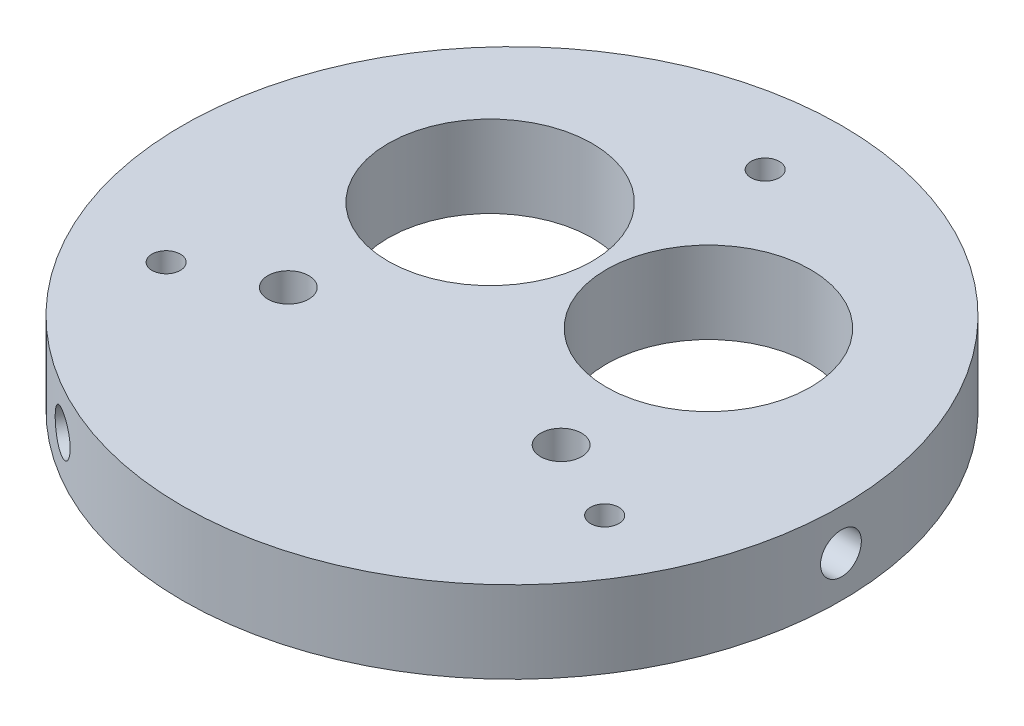
SolidWorks part; units mm, degrees
material "G10 Fiberglass"
ref_plane "Front Plane" through (0, 0, 0) normal (0, 0, 1) x (1, 0, 0)
ref_plane "Top Plane" through (0, 0, 0) normal (0, 1, 0) x (1, 0, 0)
ref_plane "Right Plane" through (0, 0, 0) normal (1, 0, 0) x (0, 0, -1)
sketch "Sketch1" plane through (0, 0, 0) normal (0, 1, 0) x (1, 0, 0)
  circle A0 centre (0, 0) radius 38.354
  dimension "D1" = 76.708
extrude "Boss-Extrude1" add sketch "Sketch1" along normal blind 9.525
sketch "Sketch2" plane through (0, 9.525, 0) normal (0, 1, 0) x (1, 0, 0)
  line L0 (12.7, 10.16) -> (-12.7, 10.16) construction
  line L3 (0, 6.35) -> (0, -19.05) construction
  line L4 (-14.6936, 35.4278) -> (-10.8624, 36.7836) construction
  line L5 (-14.6936, 35.4278) -> (-12.0454, 27.9451) construction
  line L6 (-10.8624, 36.7836) -> (-8.2143, 29.3009) construction
  line L7 (-12.0454, 27.9451) -> (-8.2143, 29.3009) construction
  line L8 (37.9022, -4.9723) -> (30.0979, -3.5244) construction
  line L9 (37.9022, -4.9723) -> (37.1609, -8.9682) construction
  line L10 (37.1609, -8.9682) -> (29.3566, -7.5202) construction
  line L11 (30.0979, -3.5244) -> (29.3566, -7.5202) construction
  line L12 (-23.3832, -30.3216) -> (-18.2271, -24.2869) construction
  line L13 (-23.3832, -30.3216) -> (-26.473, -27.6817) construction
  line L14 (-26.473, -27.6817) -> (-21.3169, -21.6469) construction
  line L15 (-18.2271, -24.2869) -> (-21.3169, -21.6469) construction
  line L16 (0, 10.16) -> (0, -18.415) construction
  line L17 (-12.7, 10.16) -> (12.7, 10.16) construction
  line L18 (-12.7, 24.13) -> (12.7, 24.13) construction
  line L19 (-12.7, -3.81) -> (12.7, -3.81) construction
  circle A0 centre (0, 0) radius 29.464 construction
  circle A1 centre (0, 29.464) radius 1.651
  circle A2 centre (25.5166, -14.732) radius 1.651
  circle A3 centre (-25.5166, -14.732) radius 1.651
  circle A4 centre (0, -18.415) radius 4.1275
  circle A7 centre (0, 0) radius 38.354 construction
  circle A8 centre (-12.7, 10.16) radius 11.8745
  circle A9 centre (12.7, 10.16) radius 11.8745
  circle A10 centre (0, 20.32) radius 3.175
  circle A11 centre (0, 0) radius 3.175
  arc A12 (-12.7, 24.13) -> (-12.7, -3.81) centre (-12.7, 10.16) ccw construction
  arc A13 (12.7, -3.81) -> (12.7, 24.13) centre (12.7, 10.16) ccw construction
  point P11 (0, 0)
  point P36 (-0.0582, 0.0446)
  point P38 (0, 10.16)
  dimension "D1" = 3.302
  dimension "D2" = 58.928
  dimension "D11" = 8.255
  dimension "D4" = 23.749
  dimension "D5" = 23.749
  dimension "D13" = 6.35
  dimension "D14" = 6.35
  dimension "D7" = 4.064
  dimension "D8" = 7.9375
  dimension "D6" = 10.16
  dimension "D10" = 25.4
  dimension "D12" = 28.575
  dimension "D15" = 27.94
  dimension "D17" = 3.81
  dimension "D16" = 3.81
  dimension "D3" = 3
  dimension "D9" = 3
extrude "Cut-Extrude1" cut sketch "Sketch2" against normal through all contours A1 | A3 | A8 | A9 | A2 region at (0, 9.525, -29.464) region at (25.5166, 9.525, 14.732) region at (-25.5166, 9.525, 14.732) region at (-12.7, 9.525, -10.16) region at (12.7, 9.525, -10.16)
ref_plane "Plane1" through (-19.177, 0, -33.2155) normal (-0.5, 0, -0.866) x (0, -1, 0)
sketch "Sketch4" plane through (-19.177, 0, -33.2155) normal (-0.5, 0, -0.866) x (0, -1, 0)
  circle A0 centre (-4.7625, 0) radius 2.3749
  dimension "D1" = 4.7625
  dimension "D2" = 4.7498
extrude "Cut-Extrude2" cut sketch "Sketch4" against normal blind 6.35
ref_axis "Axis1" through (0, 10.0012, 0) along (0, -1, 0)
pattern_circular "CirPattern1" count 3 over 360 about axis through (0, 10.0012, 0) along (0, -1, 0) of "Cut-Extrude2"
sketch "Sketch5" plane through (0, 9.525, 0) normal (0, 1, 0) x (1, 0, 0)
  line L0 (15.875, -10.16) -> (-15.875, -10.16) construction
  line L1 (0, 0) -> (0, -10.16) construction
  circle A0 centre (-15.875, -10.16) radius 2.3813
  circle A1 centre (15.875, -10.16) radius 2.3812
  dimension "D1" = 4.7625
  dimension "D2" = 4.7625
  dimension "D3" = 10.16
  dimension "D4" = 31.75
extrude "Cut-Extrude3" cut sketch "Sketch5" against normal through all both
equation "\"D5@Sketch2\"=\"D4@Sketch2\""
equation "\"D4@Sketch2\"=0.925in+0.01"
equation "\"D13@Sketch2\"=\"D14@Sketch2\""
equation "\"D16@Sketch2\"=\"D17@Sketch2\""
